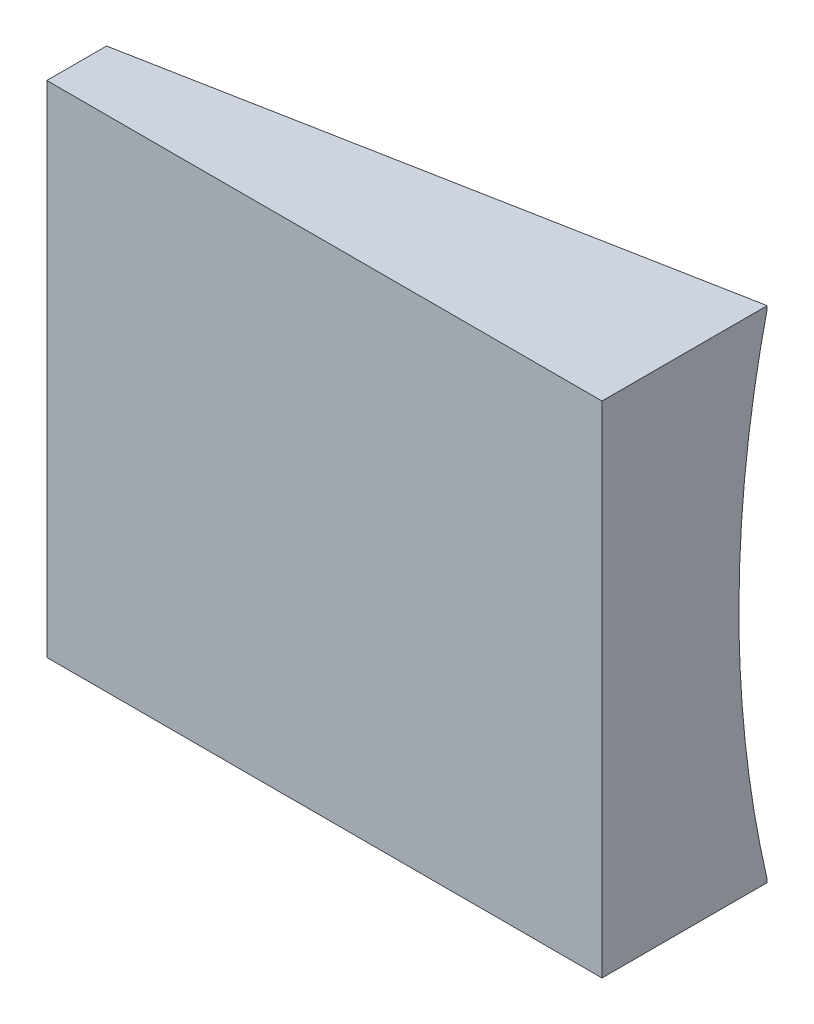
SolidWorks part; units mm, degrees
ref_plane "Plan de face" through (0, 0, 0) normal (0, 0, 1) x (1, 0, 0)
ref_plane "Plan de dessus" through (0, 0, 0) normal (0, 1, 0) x (1, 0, 0)
ref_plane "Plan de droite" through (0, 0, 0) normal (1, 0, 0) x (0, 0, -1)
sketch "Esquisse1" plane through (0, 0, 0) normal (0, 0, 1) x (1, 0, 0)
  line L1 (0, -6) -> (20, -6)
  line L2 (0, -6) -> (0, 12)
  line L3 (0, 12) -> (20, 12)
  line L4 (20, -6) -> (20, 12)
  dimension "D1" = 20
  dimension "D2" = 18
extrude "Boss.-Extru.1" add sketch "Esquisse1" along normal blind 6
sketch "Esquisse2" plane through (0, 12, 0) normal (0, 1, 0) x (1, 0, 0)
  line L0 (20.0456, -0.0409) -> (0, -3.849)
  line L1 (0, -6) -> (0, 0) construction
  line L2 (0, -3.849) -> (0, 0)
extrude "Enlèv. mat.-Extru.1" cut sketch "Esquisse2" against normal through all and the other way through all flip side to cut
sketch "Esquisse4" plane through (0.7057, 0, 3.715) normal (-0.1866, 0, -0.9824) x (-0.9824, 0, 0.1866)
  line L0 (-19.6393, -6) -> (-19.6393, 12) construction
  line L1 (-19.6393, 11.9) -> (1.1198, 11.9)
  line L2 (-19.6393, 11.9) -> (-19.6393, -5.9)
  line L3 (-19.6393, -5.9) -> (1.1198, -5.9)
  line L4 (1.1198, 11.9) -> (1.1198, -5.9)
  line L6 (-19.6393, 12) -> (0.7184, 12) construction
  line L7 (0.7184, -6) -> (-19.6393, -6) construction
  line L8 (1.1198, 12) -> (1.1198, -6) construction
  dimension "D1" = 0
  dimension "D2" = 0
  dimension "D3" = 0.1
  dimension "D4" = 0.1
extrude "Enlèv. mat.-Extru.3" cut sketch "Esquisse4" against normal blind 1
fillet "Congé2" radius 40 2 edges at (10, 11.9, 2.9672) (10, -5.9, 2.9672)
